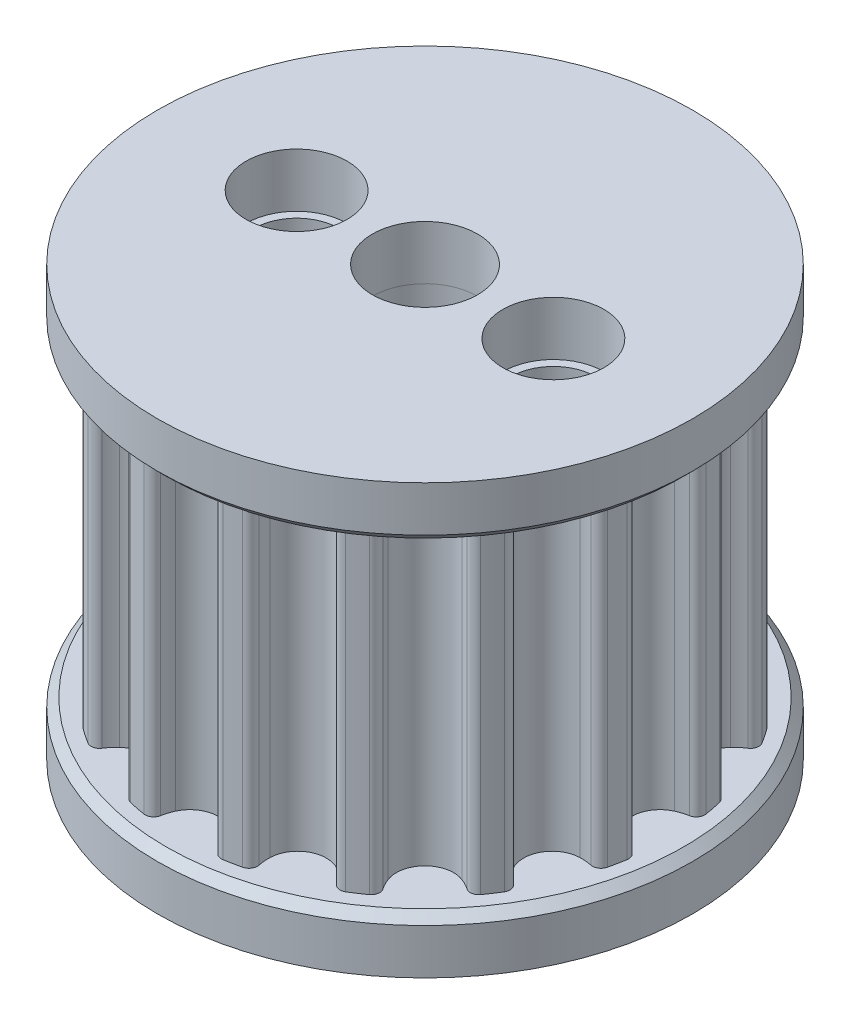
SolidWorks part; units mm, degrees
material "Alum Plate"
ref_plane "Front Plane" through (0, 0, 0) normal (0, 0, 1) x (1, 0, 0)
ref_plane "Top Plane" through (0, 0, 0) normal (0, 1, 0) x (1, 0, 0)
ref_plane "Right Plane" through (0, 0, 0) normal (1, 0, 0) x (0, 0, -1)
other "Bounding Box"
ref_plane "Default Plane" through (-8.9266, -12.7485, 0) normal (-0.1736, 0.9848, 0) x (0.9848, 0.1736, 0)
sketch "Sketch1" plane through (0, 0, 0) normal (0, 1, 0) x (1, 0, 0)
  line L0 (0, -7.8245) -> (0, 0) construction
  circle A0 centre (0, 0) radius 1.5625
  arc B0 (-1.8508, -6.777) -> (-1.6633, -7.0715) centre (-1.6061, -6.8282) ccw
  arc B1 (-1.6633, -7.0715) -> (-1.1695, -7.1697) centre (0, 0) ccw
  arc B2 (-1.1695, -7.1697) -> (-0.8836, -6.9694) centre (-1.1292, -6.923) ccw
  arc B3 (-0.7739, -6.6229) -> (-0.8836, -6.9694) centre (0.61, -7.2516) ccw
  arc B4 (0.7739, -6.6229) -> (-0.7739, -6.6229) centre (0, -6.9745) ccw
  arc B5 (0.8836, -6.9694) -> (0.7739, -6.6229) centre (-0.61, -7.2516) ccw
  arc B6 (0.8836, -6.9694) -> (1.1695, -7.1697) centre (1.1292, -6.923) ccw
  arc B7 (1.1695, -7.1697) -> (1.6633, -7.0715) centre (0, 0) ccw
  arc B8 (1.6633, -7.0715) -> (1.8508, -6.777) centre (1.6061, -6.8282) ccw
  arc B9 (1.8195, -6.4149) -> (1.8508, -6.777) centre (3.3386, -6.4662) ccw
  arc B10 (3.2495, -5.8226) -> (1.8195, -6.4149) centre (2.669, -6.4436) ccw
  arc B11 (3.4834, -6.1008) -> (3.2495, -5.8226) centre (2.2115, -6.9331) ccw
  arc B12 (3.4834, -6.1008) -> (3.8242, -6.1764) centre (3.6926, -5.9639) ccw
  arc B13 (3.8242, -6.1764) -> (4.2428, -5.8967) centre (0, 0) ccw
  arc B14 (4.2428, -5.8967) -> (4.3033, -5.5529) centre (4.0968, -5.6938) ccw
  arc B15 (4.1359, -5.2303) -> (4.3033, -5.5529) centre (5.559, -4.6963) ccw
  arc B16 (5.2303, -4.1359) -> (4.1359, -5.2303) centre (4.9317, -4.9317) ccw
  arc B17 (5.5529, -4.3033) -> (5.2303, -4.1359) centre (4.6963, -5.559) ccw
  arc B18 (5.5529, -4.3033) -> (5.8967, -4.2428) centre (5.6938, -4.0968) ccw
  arc B19 (5.8967, -4.2428) -> (6.1764, -3.8242) centre (0, 0) ccw
  arc B20 (6.1764, -3.8242) -> (6.1008, -3.4834) centre (5.9639, -3.6926) ccw
  arc B21 (5.8226, -3.2495) -> (6.1008, -3.4834) centre (6.9331, -2.2115) ccw
  arc B22 (6.4149, -1.8195) -> (5.8226, -3.2495) centre (6.4436, -2.669) ccw
  arc B23 (6.777, -1.8508) -> (6.4149, -1.8195) centre (6.4662, -3.3386) ccw
  arc B24 (6.777, -1.8508) -> (7.0715, -1.6633) centre (6.8282, -1.6061) ccw
  arc B25 (7.0715, -1.6633) -> (7.1697, -1.1695) centre (0, 0) ccw
  arc B26 (7.1697, -1.1695) -> (6.9694, -0.8836) centre (6.923, -1.1292) ccw
  arc B27 (6.6229, -0.7739) -> (6.9694, -0.8836) centre (7.2516, 0.61) ccw
  arc B28 (6.6229, 0.7739) -> (6.6229, -0.7739) centre (6.9745, 0) ccw
  arc B29 (6.9694, 0.8836) -> (6.6229, 0.7739) centre (7.2516, -0.61) ccw
  arc B30 (6.9694, 0.8836) -> (7.1697, 1.1695) centre (6.923, 1.1292) ccw
  arc B31 (7.1697, 1.1695) -> (7.0715, 1.6633) centre (0, 0) ccw
  arc B32 (7.0715, 1.6633) -> (6.777, 1.8508) centre (6.8282, 1.6061) ccw
  arc B33 (6.4149, 1.8195) -> (6.777, 1.8508) centre (6.4662, 3.3386) ccw
  arc B34 (5.8226, 3.2495) -> (6.4149, 1.8195) centre (6.4436, 2.669) ccw
  arc B35 (6.1008, 3.4834) -> (5.8226, 3.2495) centre (6.9331, 2.2115) ccw
  arc B36 (6.1008, 3.4834) -> (6.1764, 3.8242) centre (5.9639, 3.6926) ccw
  arc B37 (6.1764, 3.8242) -> (5.8967, 4.2428) centre (0, 0) ccw
  arc B38 (5.8967, 4.2428) -> (5.5529, 4.3033) centre (5.6938, 4.0968) ccw
  arc B39 (5.2303, 4.1359) -> (5.5529, 4.3033) centre (4.6963, 5.559) ccw
  arc B40 (4.1359, 5.2303) -> (5.2303, 4.1359) centre (4.9317, 4.9317) ccw
  arc B41 (4.3033, 5.5529) -> (4.1359, 5.2303) centre (5.559, 4.6963) ccw
  arc B42 (4.3033, 5.5529) -> (4.2428, 5.8967) centre (4.0968, 5.6938) ccw
  arc B43 (4.2428, 5.8967) -> (3.8242, 6.1764) centre (0, 0) ccw
  arc B44 (3.8242, 6.1764) -> (3.4834, 6.1008) centre (3.6926, 5.9639) ccw
  arc B45 (3.2495, 5.8226) -> (3.4834, 6.1008) centre (2.2115, 6.9331) ccw
  arc B46 (1.8195, 6.4149) -> (3.2495, 5.8226) centre (2.669, 6.4436) ccw
  arc B47 (1.8508, 6.777) -> (1.8195, 6.4149) centre (3.3386, 6.4662) ccw
  arc B48 (1.8508, 6.777) -> (1.6633, 7.0715) centre (1.6061, 6.8282) ccw
  arc B49 (1.6633, 7.0715) -> (1.1695, 7.1697) centre (0, 0) ccw
  arc B50 (1.1695, 7.1697) -> (0.8836, 6.9694) centre (1.1292, 6.923) ccw
  arc B51 (0.7739, 6.6229) -> (0.8836, 6.9694) centre (-0.61, 7.2516) ccw
  arc B52 (-0.7739, 6.6229) -> (0.7739, 6.6229) centre (0, 6.9745) ccw
  arc B53 (-0.8836, 6.9694) -> (-0.7739, 6.6229) centre (0.61, 7.2516) ccw
  arc B54 (-0.8836, 6.9694) -> (-1.1695, 7.1697) centre (-1.1292, 6.923) ccw
  arc B55 (-1.1695, 7.1697) -> (-1.6633, 7.0715) centre (0, 0) ccw
  arc B56 (-1.6633, 7.0715) -> (-1.8508, 6.777) centre (-1.6061, 6.8282) ccw
  arc B57 (-1.8195, 6.4149) -> (-1.8508, 6.777) centre (-3.3386, 6.4662) ccw
  arc B58 (-3.2495, 5.8226) -> (-1.8195, 6.4149) centre (-2.669, 6.4436) ccw
  arc B59 (-3.4834, 6.1008) -> (-3.2495, 5.8226) centre (-2.2115, 6.9331) ccw
  arc B60 (-3.4834, 6.1008) -> (-3.8242, 6.1764) centre (-3.6926, 5.9639) ccw
  arc B61 (-3.8242, 6.1764) -> (-4.2428, 5.8967) centre (0, 0) ccw
  arc B62 (-4.2428, 5.8967) -> (-4.3033, 5.5529) centre (-4.0968, 5.6938) ccw
  arc B63 (-4.1359, 5.2303) -> (-4.3033, 5.5529) centre (-5.559, 4.6963) ccw
  arc B64 (-5.2303, 4.1359) -> (-4.1359, 5.2303) centre (-4.9317, 4.9317) ccw
  arc B65 (-5.5529, 4.3033) -> (-5.2303, 4.1359) centre (-4.6963, 5.559) ccw
  arc B66 (-5.5529, 4.3033) -> (-5.8967, 4.2428) centre (-5.6938, 4.0968) ccw
  arc B67 (-5.8967, 4.2428) -> (-6.1764, 3.8242) centre (0, 0) ccw
  arc B68 (-6.1764, 3.8242) -> (-6.1008, 3.4834) centre (-5.9639, 3.6926) ccw
  arc B69 (-5.8226, 3.2495) -> (-6.1008, 3.4834) centre (-6.9331, 2.2115) ccw
  arc B70 (-6.4149, 1.8195) -> (-5.8226, 3.2495) centre (-6.4436, 2.669) ccw
  arc B71 (-6.777, 1.8508) -> (-6.4149, 1.8195) centre (-6.4662, 3.3386) ccw
  arc B72 (-6.777, 1.8508) -> (-7.0715, 1.6633) centre (-6.8282, 1.6061) ccw
  arc B73 (-7.0715, 1.6633) -> (-7.1697, 1.1695) centre (0, 0) ccw
  arc B74 (-7.1697, 1.1695) -> (-6.9694, 0.8836) centre (-6.923, 1.1292) ccw
  arc B75 (-6.6229, 0.7739) -> (-6.9694, 0.8836) centre (-7.2516, -0.61) ccw
  arc B76 (-6.6229, -0.7739) -> (-6.6229, 0.7739) centre (-6.9745, 0) ccw
  arc B77 (-6.9694, -0.8836) -> (-6.6229, -0.7739) centre (-7.2516, 0.61) ccw
  arc B78 (-6.9694, -0.8836) -> (-7.1697, -1.1695) centre (-6.923, -1.1292) ccw
  arc B79 (-7.1697, -1.1695) -> (-7.0715, -1.6633) centre (0, 0) ccw
  arc B80 (-7.0715, -1.6633) -> (-6.777, -1.8508) centre (-6.8282, -1.6061) ccw
  arc B81 (-6.4149, -1.8195) -> (-6.777, -1.8508) centre (-6.4662, -3.3386) ccw
  arc B82 (-5.8226, -3.2495) -> (-6.4149, -1.8195) centre (-6.4436, -2.669) ccw
  arc B83 (-6.1008, -3.4834) -> (-5.8226, -3.2495) centre (-6.9331, -2.2115) ccw
  arc B84 (-6.1008, -3.4834) -> (-6.1764, -3.8242) centre (-5.9639, -3.6926) ccw
  arc B85 (-6.1764, -3.8242) -> (-5.8967, -4.2428) centre (0, 0) ccw
  arc B86 (-5.8967, -4.2428) -> (-5.5529, -4.3033) centre (-5.6938, -4.0968) ccw
  arc B87 (-5.2303, -4.1359) -> (-5.5529, -4.3033) centre (-4.6963, -5.559) ccw
  arc B88 (-4.1359, -5.2303) -> (-5.2303, -4.1359) centre (-4.9317, -4.9317) ccw
  arc B89 (-4.3033, -5.5529) -> (-4.1359, -5.2303) centre (-5.559, -4.6963) ccw
  arc B90 (-4.3033, -5.5529) -> (-4.2428, -5.8967) centre (-4.0968, -5.6938) ccw
  arc B91 (-4.2428, -5.8967) -> (-3.8242, -6.1764) centre (0, 0) ccw
  arc B92 (-3.8242, -6.1764) -> (-3.4834, -6.1008) centre (-3.6926, -5.9639) ccw
  arc B93 (-3.2495, -5.8226) -> (-3.4834, -6.1008) centre (-2.2115, -6.9331) ccw
  arc B94 (-1.8195, -6.4149) -> (-3.2495, -5.8226) centre (-2.669, -6.4436) ccw
  arc B95 (-1.8508, -6.777) -> (-1.8195, -6.4149) centre (-3.3386, -6.4662) ccw
  dimension "D1" = 3.125
sketch_block_instance "Block-GT2 16 Tooth Profile-1"
sketch_block "Block-GT2 16 Tooth Profile" parameters "D1"=2.1152
extrude "Boss-Extrude1" add sketch "Sketch1" along normal mid plane 9.525
sketch "Sketch2" plane through (0, -4.7625, 0) normal (0, -1, 0) x (1, 0, 0)
  circle A0 centre (0, 0) radius 7.9375
  circle A1 centre (0, 0) radius 1.5625 construction
  circle A2 centre (0, 0) radius 1.5625
  dimension "D1" = 15.875
extrude "Boss-Extrude2" add sketch "Sketch2" along normal blind 1.6002 separate body
sketch "Sketch3" plane through (0, -6.3627, 0) normal (0, -1, 0) x (1, 0, 0)
  line L0 (0, 0) -> (3.81, 0) construction
  line L1 (0, 0) -> (-3.81, 0) construction
  circle A0 centre (-3.81, 0) radius 1.5
  circle A1 centre (3.81, 0) radius 1.5
  point P6 (-3.883, 0)
  dimension "D1" = 3
  dimension "D2" = 3.81
extrude "Cut-Extrude1" cut sketch "Sketch3" against normal through all
sketch "Sketch4" plane through (0, -4.7625, 0) normal (0, -1, 0) x (1, 0, 0)
  circle A0 centre (-3.81, 0) radius 1.25
  circle A1 centre (3.81, 0) radius 1.25
  dimension "D1" = 2.5
extrude "Cut-Extrude2" cut sketch "Sketch4" against normal through all
chamfer "Chamfer1" distance 0.254 angle 45 1 edges at (0, -4.7625, -7.9375)
mirror "Mirror2" about plane through (0, 0, 0) normal (0, 1, 0) of bodies 107 105
